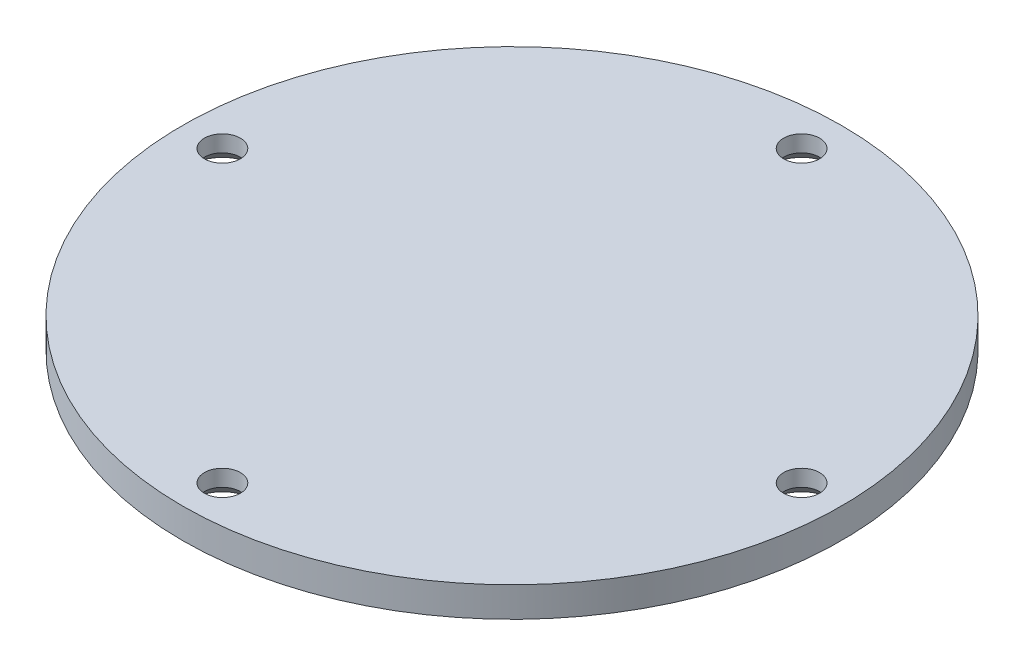
SolidWorks part; units mm, degrees
ref_plane "Front Plane" through (0, 0, 0) normal (0, 0, 1) x (1, 0, 0)
ref_plane "Top Plane" through (0, 0, 0) normal (0, 1, 0) x (1, 0, 0)
ref_plane "Right Plane" through (0, 0, 0) normal (1, 0, 0) x (0, 0, -1)
sketch "Sketch1" plane through (0, 0, 0) normal (0, 1, 0) x (1, 0, 0)
  circle A0 centre (0, 0) radius 33
  circle A1 centre (-29, 0) radius 1.5
  circle A2 centre (0, 0) radius 29 construction
  circle A3 centre (0, 29) radius 1.5
  circle A4 centre (29, 0) radius 1.5
  circle A5 centre (0, -29) radius 1.5
  point P6 (27.2253, 0)
  point P7 (0, 0)
  point P8 (0, 0)
  point P15 (0, 0)
  point P16 (0, 0)
  point P17 (0, 0)
  dimension "D1" = 66
  dimension "D2" = 4
  dimension "D3" = 3
  dimension "D4" = 4
extrude "Boss-Extrude1" add sketch "Sketch1" along normal blind 3
hole_wizard "CSK for M3 Flat Head Machine Screw1" positions "Sketch2" profile "Sketch3" countersink size "M3" standard "ANSI Metric" end condition through all
sketch "Sketch2" plane through (0, 0, 0) normal (0, -1, 0) x (-1, 0, 0)
  point P0 (0, -29)
  point P3 (29, 0)
  point P6 (0, 29)
  point P9 (-29, 0)
sketch "Sketch3" plane through (0, 0, 29) normal (1, 0, 0) x (0, 0, -1)
  line L0 (0, 0) -> (0, 3)
  line L1 (0, 3) -> (1.8, 3)
  line L2 (1.8, 3) -> (1.8, 1.35)
  line L3 (1.8, 1.35) -> (3.15, 0)
  line L5 (3.15, 0) -> (0, 0)
  line L6 (-1.8, 1.35) -> (-3.15, 0) construction
  line L11 (0, -6.35) -> (0, 107.95) construction
  dimension "Thru Hole Dia." = 3.6
  dimension "Thru Hole Depth" = 3
  dimension "Near C'Sink Dia." = 6.3
  dimension "Near C'Sink Angle" = 90
